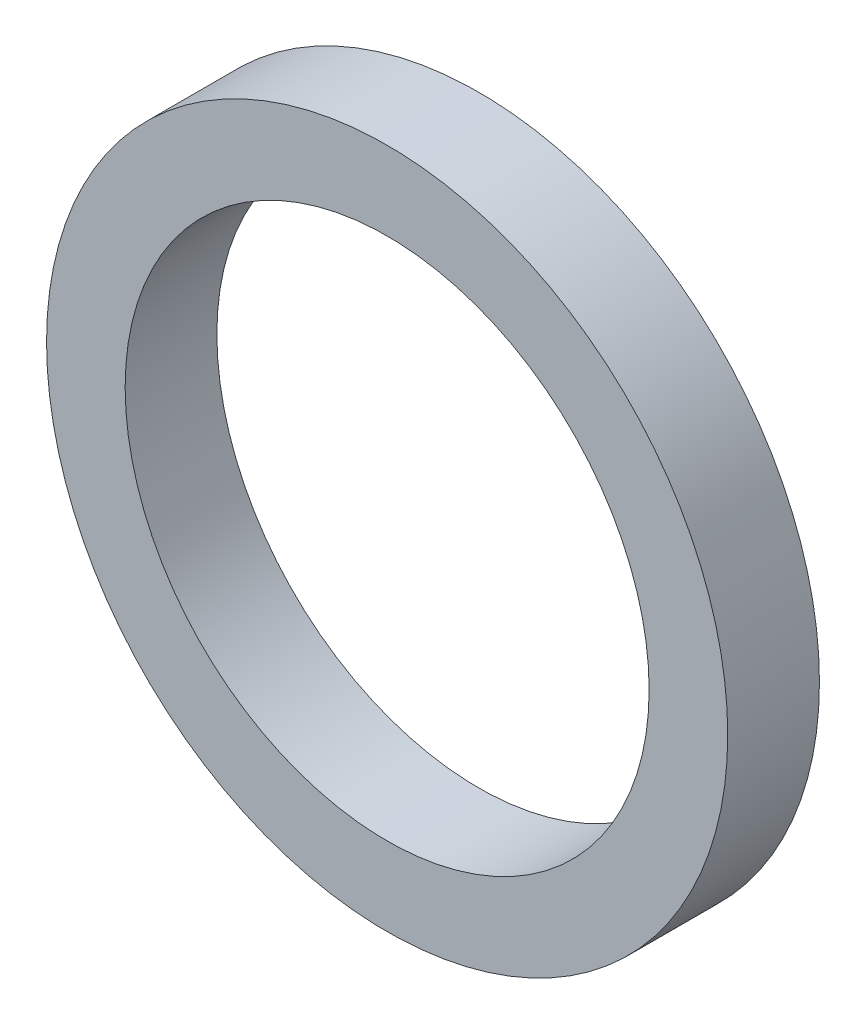
SolidWorks part; units mm, degrees
ref_plane "Plan de face" through (0, 0, 0) normal (0, 0, 1) x (1, 0, 0)
ref_plane "Plan de dessus" through (0, 0, 0) normal (0, 1, 0) x (1, 0, 0)
ref_plane "Plan de droite" through (0, 0, 0) normal (1, 0, 0) x (0, 0, -1)
sketch "Sketch1" plane through (0, 0, 0) normal (0, 0, 1) x (1, 0, 0)
  circle A0 centre (0, 0) radius 10
  circle A1 centre (0, 0) radius 13
  dimension "D1" = 20
  dimension "D2" = 26
extrude "Boss-Extrude1" add sketch "Sketch1" along normal blind 3.5
